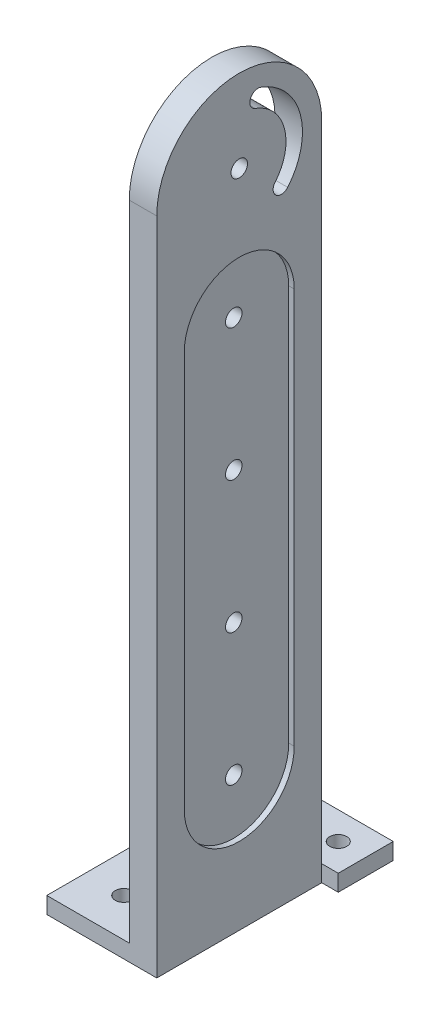
SolidWorks part; units mm, degrees
ref_plane "前视基准面" through (0, 0, 0) normal (0, 0, 1) x (1, 0, 0)
ref_plane "上视基准面" through (0, 0, 0) normal (0, 1, 0) x (1, 0, 0)
ref_plane "右视基准面" through (0, 0, 0) normal (1, 0, 0) x (0, 0, -1)
sketch "草图1" plane through (0, 0, 0) normal (1, 0, 0) x (0, 0, -1)
  line L0 (-15, 0) -> (15, 0)
  line L1 (-15, 0) -> (-15, 120)
  line L2 (15, 0) -> (15, 120)
  line L10 (0, 120) -> (-10, 120) construction
  line L11 (0, 120) -> (-3.4202, 129.3969) construction
  line L12 (0, 120) -> (-7.6604, 113.5721) construction
  circle A2 centre (0, 24) radius 1.5
  circle A3 centre (0, 48) radius 1.5
  circle A4 centre (0, 72) radius 1.5
  circle A5 centre (0, 96) radius 1.5
  circle A9 centre (0, 120) radius 1.5
  circle A10 centre (0, 120) radius 10 construction
  arc A11 (-8.8095, 112.6079) -> (-6.5114, 114.5363) centre (-7.6604, 113.5721) ccw construction
  arc A12 (-2.9072, 127.9874) -> (-3.9332, 130.8065) centre (-3.4202, 129.3969) ccw construction
  arc A13 (-3.9332, 130.8065) -> (-8.8095, 112.6079) centre (0, 120) ccw construction
  arc A14 (-2.9072, 127.9874) -> (-6.5114, 114.5363) centre (0, 120) ccw construction
  arc A16 (2.9072, 127.9874) -> (3.9332, 130.8065) centre (3.4202, 129.3969) cw
  arc A19 (8.8095, 112.6079) -> (6.5114, 114.5363) centre (7.6604, 113.5721) cw
  arc A20 (2.9072, 127.9874) -> (6.5114, 114.5363) centre (0, 120) cw
  arc A21 (3.9332, 130.8065) -> (8.8095, 112.6079) centre (0, 120) cw
  arc A22 (15, 120) -> (-15, 120) centre (0, 120) ccw
  point P3 (0, 0)
  dimension "D5" = 1.5
  dimension "D7" = 1.5
  dimension "D4" = 3
  dimension "D9" = 3
  dimension "D11" = 40
  dimension "D3" = 15
  dimension "D8" = 1.5
  dimension "D1" = 30
  dimension "D2" = 120
  dimension "D6" = 24
  dimension "D10" = 15
  dimension "D12" = 70
  dimension "D13" = 24
  dimension "D14" = 24
  dimension "D15" = 24
extrude "凸台-拉伸2" add sketch "草图1" against normal blind 5
ref_plane "基准面1" through (-5, 0, 0) normal (-1, 0, 0) x (0, 0, 1)
ref_plane "基准面3" through (-30, 0, 0) normal (-1, 0, 0) x (0, 0, 1)
ref_plane "基准面6" through (0, 0, 0) normal (0, -1, 0) x (-1, 0, 0)
sketch "草图5" plane through (0, 0, 0) normal (0, -1, 0) x (-1, 0, 0)
  line L0 (0, -15) -> (20, -15)
  line L1 (20, -15) -> (20, 15)
  line L3 (0, 15) -> (0, -15)
  line L4 (0, 15) -> (-3, 15)
  line L5 (-3, 15) -> (-3, 25)
  line L6 (-3, 25) -> (20, 25)
  line L9 (20, 15) -> (20, 25)
  dimension "D1" = 20
  dimension "D2" = 30
  dimension "D3" = 20
  dimension "D6" = 3
  dimension "D7" = 10
extrude "凸台-拉伸3" add sketch "草图5" against normal blind 3
sketch "草图6" plane through (0, 0, 0) normal (0, -1, 0) x (1, 0, 0)
  line L1 (-20, 15) -> (0, 15) construction
  line L3 (-20, 15) -> (-20, -25) construction
  line L4 (-20, -25) -> (3, -25) construction
  line L6 (3, -25) -> (3, -15) construction
  circle A1 centre (-13, 8) radius 1.55
  circle A3 centre (-2, -20) radius 1.55
  circle A4 centre (-13, -3) radius 1.55
  dimension "D1" = 3.1
  dimension "D4" = 3.1
  dimension "D2" = 3.1
  dimension "D3" = 11
  dimension "D5" = 7
  dimension "D6" = 7
  dimension "D7" = 5
  dimension "D9" = 5
extrude "切除-拉伸2" cut sketch "草图6" against normal blind 10
sketch "草图7" plane through (-5, 0, 0) normal (-1, 0, 0) x (0, 0, 1)
  line L0 (15, 3) -> (-15, 3) construction
  line L5 (-11.8, 3) -> (-8.8, 3)
  line L6 (-11.8, 3) -> (-11.8, 44)
  line L7 (-11.8, 44) -> (-8.8, 44)
  line L8 (-8.8, 3) -> (-8.8, 44)
  line L9 (-15, 3) -> (-15, 120) construction
  dimension "D1" = 3
  dimension "D2" = 41
  dimension "D3" = 3.2
extrude "凸台-拉伸4" add sketch "草图7" along normal blind 13
sketch "草图9" plane through (0, 0, -11.8) normal (0, 0, -1) x (-1, 0, 0)
  line L0 (18, 50.5) -> (5, 63.5)
  line L1 (5, 44) -> (18, 44)
  line L2 (5, 44) -> (5, 50.5)
  line L3 (5, 3) -> (5, 120) construction
  line L5 (18, 50.5) -> (18, 44)
  line L6 (5, 63.5) -> (5, 50.5)
extrude "凸台-拉伸5" add sketch "草图9" against normal blind 3
sketch "草图10" plane through (0, 0, -11.8) normal (0, 0, -1) x (-1, 0, 0)
  line L3 (18, 50.5) -> (18, 3) construction
  line L4 (18, 50.5) -> (5, 50.5) construction
  line L5 (5, 3) -> (5, 120) construction
  circle A0 centre (11.5, 44) radius 1.6
  circle A1 centre (11.5, 7) radius 1.6
  dimension "D1" = 3.2
  dimension "D2" = 3.2
  dimension "D3" = 37
  dimension "D4" = 6.5
  dimension "D5" = 6.5
extrude "切除-拉伸3" cut sketch "草图10" against normal blind 3
sketch "草图12" plane through (0, 0, 0) normal (1, 0, 0) x (0, 0, -1)
  line L0 (-10, 24) -> (-10, 96)
  line L2 (10, 24) -> (10, 96)
  arc A0 (-10, 24) -> (10, 24) centre (0, 24) ccw
  arc A2 (10, 96) -> (-10, 96) centre (0, 96) ccw
  dimension "D1" = 20
extrude "切除-拉伸5" cut sketch "草图12" against normal blind 1
